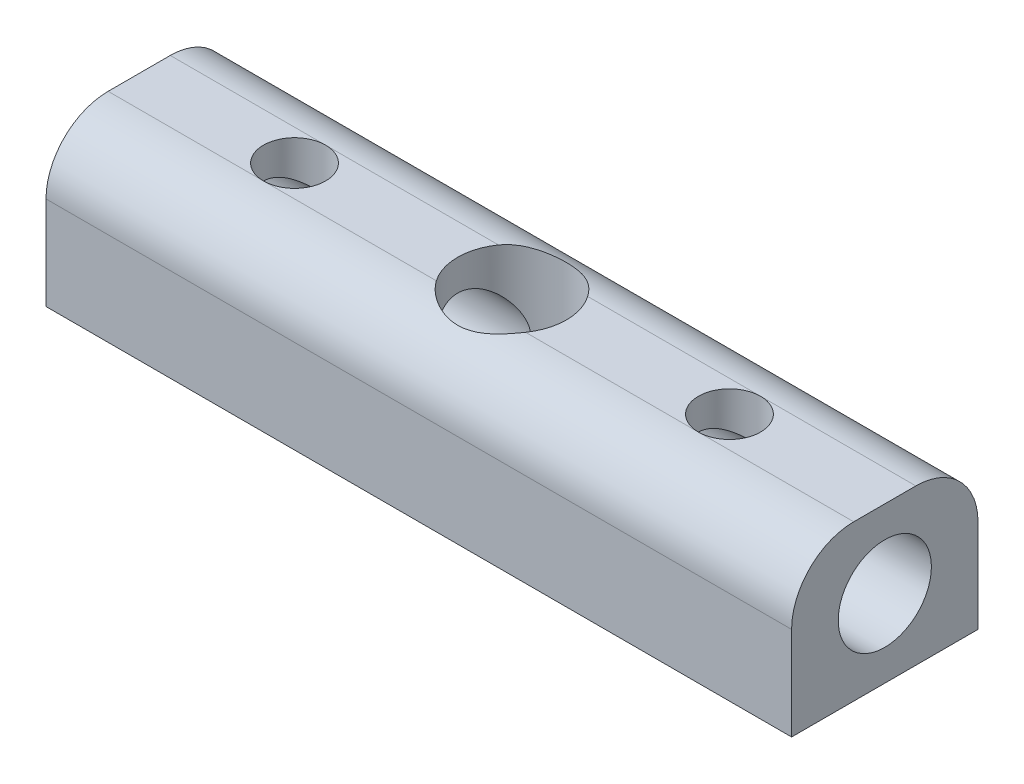
SolidWorks part; units mm, degrees
ref_plane "前视基准面" through (0, 0, 0) normal (0, 0, 1) x (1, 0, 0)
ref_plane "上视基准面" through (0, 0, 0) normal (0, 1, 0) x (1, 0, 0)
ref_plane "右视基准面" through (0, 0, 0) normal (1, 0, 0) x (0, 0, -1)
other "Configuration Table"
sketch "草图1" plane through (0, 0, 0) normal (0, 0, 1) x (1, 0, 0)
  line L1 (-12, -2.5) -> (12, -2.5)
  line L2 (-12, -2.5) -> (-12, 2.5)
  line L3 (-12, 2.5) -> (12, 2.5)
  line L4 (12, -2.5) -> (12, 2.5)
  line L5 (-12, -2.5) -> (12, 2.5) construction
  line L6 (-12, 2.5) -> (12, -2.5) construction
  point P0 (0, 0)
  dimension "D1" = 24
  dimension "D2" = 5
extrude "凸台-拉伸1" add sketch "草图1" along normal mid plane 6
sketch "草图2" plane through (12, 0, 0) normal (1, 0, 0) x (0, 0, -1)
  circle A0 centre (0, 0) radius 1.5
  dimension "D1" = 3
extrude "切除-拉伸1" cut sketch "草图2" against normal through all
sketch "草图3" plane through (0, 2.5, 0) normal (0, 1, 0) x (1, 0, 0)
  circle A0 centre (0, 0) radius 1.75
  dimension "D1" = 3.5
extrude "切除-拉伸2" cut sketch "草图3" against normal through all
sketch "草图4" plane through (0, 2.5, 0) normal (0, 1, 0) x (1, 0, 0)
  circle A0 centre (-7, 0) radius 1
  dimension "D1" = 2
  dimension "D2" = 7
extrude "切除-拉伸3" cut sketch "草图4" against normal through all
sketch "草图5" plane through (0, 2.5, 0) normal (0, 1, 0) x (1, 0, 0)
  line L0 (0, 3) -> (0, 0) construction
  line L4 (12, 3) -> (-12, 3)
  line L5 (-12, 3) -> (-12, -3)
  line L6 (-12, -3) -> (12, -3)
  line L7 (12, -3) -> (12, 3)
  line L8 (12, 3) -> (-12, 3)
  line L9 (-12, 3) -> (-12, -3)
  line L10 (-12, -3) -> (12, -3)
  line L11 (12, -3) -> (12, 3)
  circle A0 centre (-7, 0) radius 1 construction
  circle A1 centre (-7, 0) radius 1
  circle A2 centre (7, 0) radius 1
  dimension "D1" = 0
extrude "凸台-拉伸3" add sketch "草图5" along normal blind 2 contours A2 region at (7, 2.5, 0)
sketch "草图6" plane through (0, 0, -3) normal (0, 0, -1) x (-1, 0, 0)
  line L0 (-6, 2.5) -> (-6, 4.5) construction
  line L1 (-6, 2.5) -> (-6, 4.5)
  line L2 (-6, 4.5) -> (-8, 4.5) construction
  line L3 (-6, 4.5) -> (-8, 4.5)
  line L4 (-12, 2.5) -> (-12, -2.5)
  line L5 (-12, -2.5) -> (12, -2.5)
  line L6 (12, -2.5) -> (12, 2.5)
  line L7 (12, 2.5) -> (-12, 2.5)
  line L8 (-12, 2.5) -> (-12, -2.5)
  line L9 (-12, -2.5) -> (12, -2.5)
  line L10 (12, -2.5) -> (12, 2.5)
  line L11 (12, 2.5) -> (-12, 2.5)
  line L12 (-8, 4.5) -> (-8, 2.5) construction
  line L13 (-8, 4.5) -> (-8, 2.5)
  line L14 (-6, 3) -> (-8, 3)
  line L15 (-8, 3) -> (-8, 3.5)
  line L16 (-8, 3.5) -> (-6, 3.5)
  line L18 (-6, 3.5) -> (-8, 3.5)
  line L19 (-6, 3.5) -> (-6, 3)
  line L20 (-6, 3) -> (-8, 3)
  line L21 (-8, 3.5) -> (-8, 3)
  dimension "D2" = 0.5
  dimension "D1" = 0
extrude "切除-拉伸7" cut sketch "草图6" against normal blind 3 contours L16 L13 L14 L1 region at (7, 3.25, -3)
sketch "草图8" plane through (0, 4.5, 0) normal (0, 1, 0) x (1, 0, 0)
  circle A1 centre (7, 0) radius 1
  circle A2 centre (7, 0) radius 1
  dimension "D1" = 0
extrude "切除-拉伸9" cut sketch "草图8" against normal blind 10
fillet "圆角2" radius 2 2 edges at (0, 2.5, 3) (0, 2.5, -3)
